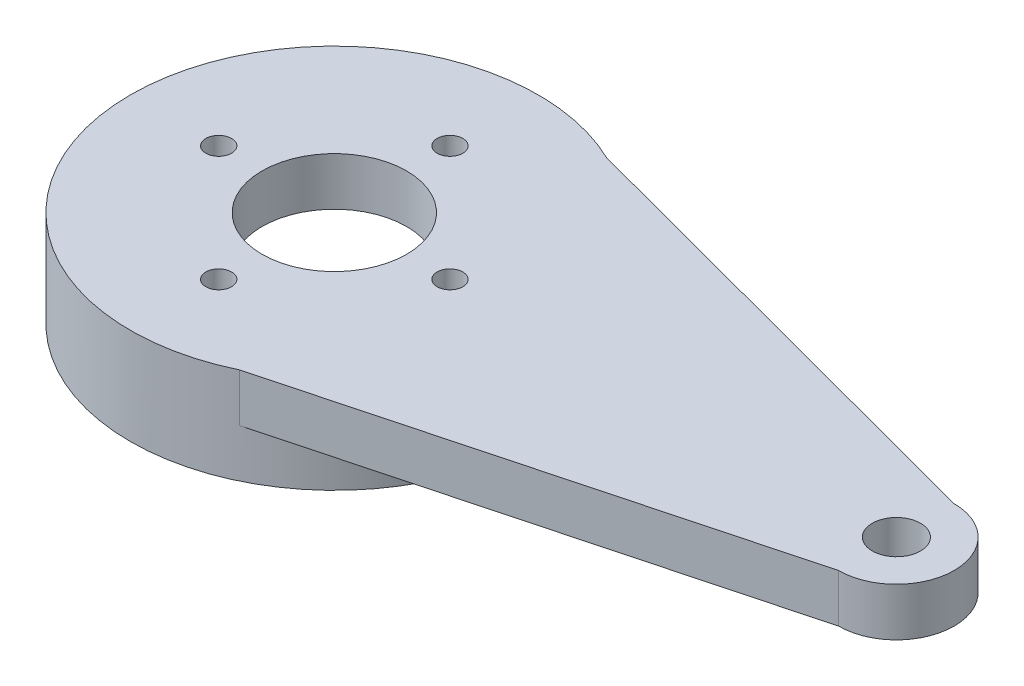
SolidWorks part; units mm, degrees
ref_plane "Front Plane" through (0, 0, 0) normal (0, 0, 1) x (1, 0, 0)
ref_plane "Top Plane" through (0, 0, 0) normal (0, 1, 0) x (1, 0, 0)
ref_plane "Right Plane" through (0, 0, 0) normal (1, 0, 0) x (0, 0, -1)
sketch "Sketch1" plane through (0, 0, 0) normal (0, 1, 0) x (1, 0, 0)
  line L1 (35, 3.6) -> (5.5261, 11.4347)
  line L2 (35, -3.6) -> (5.5261, -11.4347)
  circle A0 centre (0, -7.2) radius 0.8
  circle A1 centre (7.2, 0) radius 0.8
  circle A2 centre (0, 7.2) radius 0.8
  circle A3 centre (-7.2, 0) radius 0.8
  circle A4 centre (0, 0) radius 1.5
  circle A6 centre (0, 0) radius 10.7
  circle A7 centre (0, 0) radius 12.7
  circle A8 centre (35, 0) radius 1.5
  circle A9 centre (35, 0) radius 3.6
  point P16 (35, 3.6)
  point P22 (35, -3.6)
  dimension "D1" = 2
extrude "Boss-Extrude1" add sketch "Sketch1" along normal blind 3 contours A6 A0 A1 A2 A3 A4 | A7 A6 | A9 L1 A7 L2 | A9 A8 region at (20.2042, 0, 0) region at (37.4736, 0, -2.4736) region at (10.4538, 0, -6.5585) region at (-10.3974, 0, 0)
extrude "Boss-Extrude2" add sketch "Sketch1<3>" against normal blind 3 contours A7 A6 region at (10.4538, 0, -6.5585)
sketch "Sketch1<3>" plane through (0, 0, 0) normal (0, 1, 0) x (1, 0, 0) same geometry as "Sketch1"
sketch "Sketch2" plane through (0, 0, 0) normal (0, -1, 0) x (1, 0, 0)
  circle A0 centre (0, 0) radius 4.5
extrude "Cut-Extrude1" cut sketch "Sketch2" against normal blind 10
